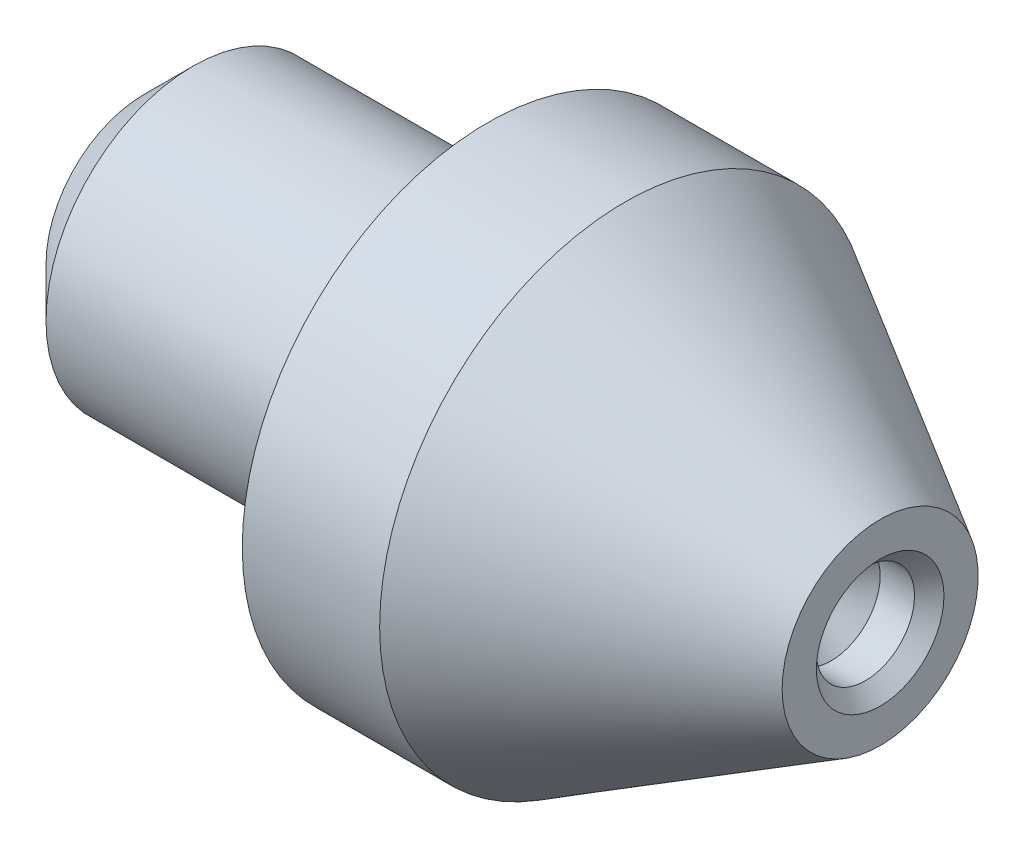
SolidWorks part; units mm, degrees
material "7075-T6 (SN)"
ref_plane "Front Plane" through (0, 0, 0) normal (0, 0, 1) x (1, 0, 0)
ref_plane "Top Plane" through (0, 0, 0) normal (0, 1, 0) x (1, 0, 0)
ref_plane "Right Plane" through (0, 0, 0) normal (1, 0, 0) x (0, 0, -1)
sketch "Sketch1" plane through (0, 0, 0) normal (0, 1, 0) x (1, 0, 0)
  line L0 (-2.4277, 0) -> (1.6908, 0) construction
  line L1 (-7, 0) -> (-7, 2)
  line L2 (-7, 2) -> (-6, 3)
  line L3 (-6, 3) -> (0, 3)
  line L4 (0, 3) -> (0, 5)
  line L5 (0, 5) -> (2.8, 5)
  line L6 (2.8, 5) -> (8, 1.9978)
  line L7 (8, 1.9978) -> (8, 0)
  line L8 (-7, 0) -> (8, 0)
  dimension "D1" = 15
  dimension "D2" = 3
  dimension "D3" = 1
  dimension "D4" = 1
  dimension "D5" = 8
  dimension "D6" = 5
  dimension "D7" = 5.2
  dimension "D8" = 30
revolve "Revolve1" add sketch "Sketch1" angle 360 about L0
sketch "Sketch2" plane through (8, 0, 0) normal (1, 0, 0) x (0, 0, -1)
  circle A0 centre (0, 0) radius 1
  dimension "D1" = 2
extrude "Cut-Extrude1" cut sketch "Sketch2" against normal blind 0.3
chamfer "Chamfer1" distance 0.3 angle 45 1 edges at (8, 0, -1)
sketch "Sketch3" plane through (7.7, 0, 0) normal (1, 0, 0) x (0, 0, -1)
  circle A1 centre (0, 0) radius 1
  circle A2 centre (0, 0) radius 1
  dimension "D1" = 0
extrude "Cut-Extrude2" cut sketch "Sketch3" against normal blind 0.7
sketch "Sketch4" plane through (7, 0, 0) normal (1, 0, 0) x (0, 0, -1)
  circle A1 centre (0, 0) radius 1
  circle A2 centre (0, 0) radius 1
  dimension "D1" = 0
extrude "Cut-Extrude3" cut sketch "Sketch4" against normal blind 1 draft 45
